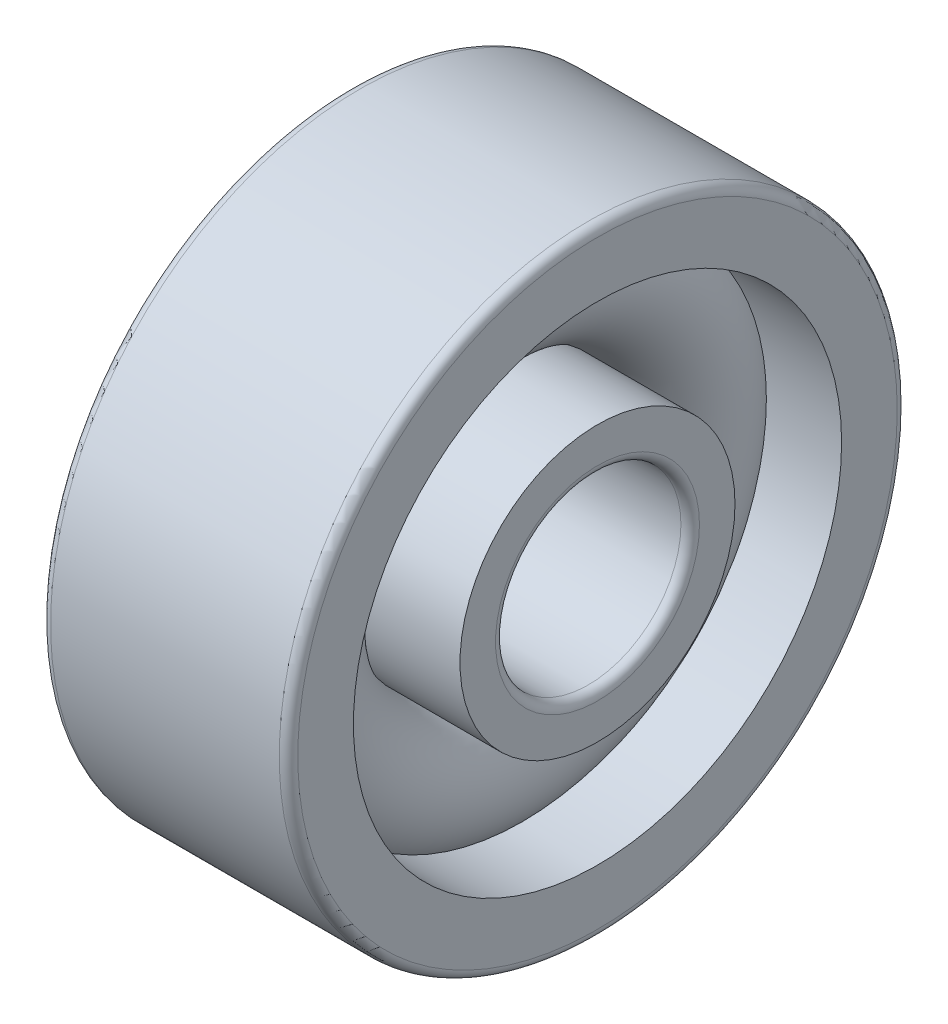
SolidWorks part; units mm, degrees
ref_plane "Plane1" through (0, 0, 0) normal (0, 0, 1) x (1, 0, 0)
ref_plane "Plane2" through (0, 0, 0) normal (0, 1, 0) x (1, 0, 0)
ref_plane "Plane3" through (0, 0, 0) normal (1, 0, 0) x (0, 0, -1)
other "Configuration Table"
sketch "Clipboard" plane through (0, 0, 0) normal (0, 0, 1) x (1, 0, 0)
  line L0 (-10, 0) -> (10, 0) construction
  line L1 (0, 0) -> (22.3471, -0.7804)
  line L2 (0, 0) -> (3.248, 0.1134)
  line L3 (0, 0) -> (22.3471, -0.7804)
  line L4 (0, 0) -> (-22.3573, -0.3902)
  dimension "BallCLRad" = 3.25
sketch "CagSpiSke" plane through (0, 0, 0) normal (0, 0, 1) x (1, 0, 0)
  line L0 (0.2625, 3.075) -> (0.2625, 3.425)
  line L1 (0.2625, 3.425) -> (-0.2625, 3.425)
  line L2 (-0.2625, 3.425) -> (-0.2625, 3.075)
  line L3 (-0.2625, 3.075) -> (0.2625, 3.075)
  line L4 (-20.6375, 0) -> (20.6375, 0) construction
  line L5 (0, 0) -> (0, 23.7692) construction
  dimension "OD" = 6.85
  dimension "ID" = 6.15
revolve "CageSpine" add sketch "CagSpiSke" angle 0.001 about L4
ref_axis "Axis1" through (-50, 0, 0) along (1, 0, 0)
sketch "CagBalSke" plane through (0, 0, 0) normal (0, 0, 1) x (1, 0, 0)
  line L0 (-1.155, 3.25) -> (1.155, 3.25)
  line L1 (-1.905, 3.25) -> (1.905, 3.25) construction
  line L2 (-10, 0) -> (10, 0) construction
  line L3 (0, 0) -> (0, 24) construction
  arc A0 (1.155, 3.25) -> (-1.155, 3.25) centre (0, 3.25) cw
  dimension "BallCLRad" = 3.25
revolve "CageBall" [suppressed] add sketch "CagBalSke" angle 360 about L1 reverse direction yes
pattern_circular "CageBalls" [suppressed] count 2 every 180 about axis through (-50, 0, 0) along (1, 0, 0)
sketch "CagTrmODSke" plane through (0, 0, 0) normal (0, 0, 1) x (1, 0, 0)
  line L0 (1.156, 3.425) -> (1.156, 4.406)
  line L1 (1.156, 4.406) -> (-1.156, 4.406)
  line L2 (-1.156, 4.406) -> (-1.156, 3.425)
  line L3 (-1.156, 3.425) -> (1.156, 3.425)
  line L4 (-20.6375, 0) -> (20.6375, 0) construction
  line L5 (0, 0) -> (0, 25) construction
  dimension "Width" = 2.312
  dimension "ID" = 6.85
  dimension "OD" = 8.812
revolve "CageTrimOD" [suppressed] cut sketch "CagTrmODSke" angle 360 about L4 reverse direction yes
sketch "CagTrmIDSke" plane through (0, 0, 0) normal (0, 0, 1) x (1, 0, 0)
  line L0 (1.156, 2.096) -> (1.156, 3.075)
  line L1 (1.156, 3.075) -> (-1.156, 3.075)
  line L2 (-1.156, 3.075) -> (-1.156, 2.096)
  line L3 (-1.156, 2.096) -> (1.156, 2.096)
  line L4 (-20.6375, 0) -> (20.6375, 0) construction
  line L5 (0, 0) -> (0, 25) construction
  dimension "Width" = 2.312
  dimension "ID" = 4.192
  dimension "OD" = 6.15
revolve "CageTrimID" [suppressed] cut sketch "CagTrmIDSke" angle 360 about L4 reverse direction yes
sketch "BalSimSke" plane through (0, 0, 0) normal (0, 0, 1) x (1, 0, 0)
  line L0 (-10, 0) -> (10, 0) construction
  line L1 (-10, 3.25) -> (10, 3.25) construction
  line L2 (0, 0) -> (0, 23) construction
  circle A0 centre (0, 3.25) radius 1.05
  dimension "BallCLRad" = 3.25
  dimension "Ball_diameter" = 2.1
revolve "BallsSimplified" add sketch "BalSimSke" angle 360 about L0
sketch "BalDetSke" plane through (0, 0, 0) normal (0, 0, 1) x (1, 0, 0)
  line L0 (-1.05, 3.25) -> (1.05, 3.25)
  line L1 (-1.905, 3.25) -> (1.905, 3.25) construction
  line L2 (0, 0) -> (0, 25) construction
  arc A0 (1.05, 3.25) -> (-1.05, 3.25) centre (0, 3.25) cw
  dimension "BallCLRad" = 3.25
  dimension "Ball_diameter" = 2.1
revolve "BallDetailed" [suppressed] add sketch "BalDetSke" angle 360 about L1 reverse direction yes
sketch "InnRacSke" plane through (0, 0, 0) normal (0, 0, 1) x (1, 0, 0)
  line L0 (-0.7487, 2.55) -> (-2, 2.55)
  line L1 (-2, 2.55) -> (-2, 1.65)
  line L2 (-1.85, 1.5) -> (1.85, 1.5)
  line L3 (2, 1.65) -> (2, 2.225)
  line L4 (0, 2.225) -> (2, 2.225)
  line L5 (-20.6375, 0) -> (20.6375, 0) construction
  line L6 (0, 0) -> (0, 30) construction
  arc A0 (-2, 1.65) -> (-1.85, 1.5) centre (-1.85, 1.65) ccw
  arc A1 (1.85, 1.5) -> (2, 1.65) centre (1.85, 1.65) ccw
  arc A2 (0, 2.225) -> (-0.7487, 2.55) centre (0, 3.25) cw
  dimension "BallCLRad" = 3.25
  dimension "Fillet_radius" = 0.15
  dimension "Ball_diameter" = 2.05
  dimension "ID" = 3
  dimension "OD" = 5.1
  dimension "Width" = 4
revolve "InnerRace" add sketch "InnRacSke" angle 360 about L5 reverse direction yes
sketch "OutRacSke" plane through (0, 0, 0) normal (0, 0, 1) x (1, 0, 0)
  line L0 (0, 4.275) -> (-2, 4.275)
  line L1 (-2, 4.275) -> (-2, 4.85)
  line L2 (-1.85, 5) -> (1.85, 5)
  line L3 (2, 4.85) -> (2, 3.95)
  line L4 (2, 3.95) -> (0.7487, 3.95)
  line L5 (-20.6375, 0) -> (20.6375, 0) construction
  line L6 (0, 0) -> (0, 30) construction
  arc A0 (-2, 4.85) -> (-1.85, 5) centre (-1.85, 4.85) cw
  arc A1 (1.85, 5) -> (2, 4.85) centre (1.85, 4.85) cw
  arc A2 (0.7487, 3.95) -> (0, 4.275) centre (0, 3.25) ccw
  dimension "BallCLRad" = 3.25
  dimension "Fillet_radius" = 0.15
  dimension "Ball_diameter" = 2.05
  dimension "Width" = 4
revolve "OuterRace" add sketch "OutRacSke" angle 360 about L5 reverse direction yes
pattern_circular "BallsDetailed" [suppressed] count 2 every 180 about axis through (-50, 0, 0) along (1, 0, 0)
equation "\"BallCLRad@Clipboard\" = ( \"OD@OutRacSke\" + \"ID@InnRacSke\" ) / 4"
equation "\"BallCLRad@BalSimSke\" = \"BallCLRad@Clipboard\""
equation "\"BallCLRad@BalDetSke\" = \"BallCLRad@Clipboard\""
equation "\"BallCLRad@InnRacSke\" = \"BallCLRad@Clipboard\""
equation "\"BallCLRad@OutRacSke\" = \"BallCLRad@Clipboard\""
equation "\"Ball_diameter@InnRacSke\" = \"Ball_diameter@BalDetSke\" - 0.05"
equation "\"Ball_diameter@OutRacSke\" = \"Ball_diameter@BalDetSke\" - 0.05"
equation "\"Ball_diameter@BalSimSke\" = \"Ball_diameter@BalDetSke\""
equation "\"Width@OutRacSke\" = \"Width@InnRacSke\""
equation "\"Fillet_radius@OutRacSke\" = \"Fillet_radius@InnRacSke\""
equation "\"Max_count@Clipboard\" = int( 3.14159265 / atn(( \"Ball_diameter@BalDetSke\" / 2) / sqr( \"BallCLRad@Clipboard\"  *  \"BallCLRad@Clipboard\" - ( \"Ball_diameter@BalDetSke\" / 2) *  ( \"Ball_diameter@BalDetSke\" / 2))))"
equation "\"Max_count@Clipboard\" = ((sgn( \"Max_count@Clipboard\" - \"Count@Clipboard\" )-1)*( \"Max_count@Clipboard\" - \"Count@Clipboard\" ))/-2+ \"Count@Clipboard\""
equation "\"Count@BallsDetailed\" = int( \"Show_count@Clipboard\" ) "
equation "\"Count@BallsDetailed\" = ((sgn( \"Count@BallsDetailed\" - \"Max_count@Clipboard\" )-1)*( \"Count@BallsDetailed\" - \"Max_count@Clipboard\" ))/-2+ \"Max_count@Clipboard\""
equation "\"Count@BallsDetailed\" = ((sgn( \"Count@BallsDetailed\" - \"Min_count@Clipboard\" )+1)*( \"Count@BallsDetailed\" - \"Min_count@Clipboard\"))/2 +\"Min_count@Clipboard\""
equation "\"Angle@BallsDetailed\" = 360.0 / \"Max_count@Clipboard\""
equation "\"BallCLRad@CagBalSke\" = \"BallCLRad@Clipboard\""
equation "\"Count@CageBalls\" = \"Count@BallsDetailed\""
equation "\"Angle@CageBalls\" = \"Angle@BallsDetailed\""
equation "\"Angle@CageSpine\" =  \"Angle@CageBalls\" * ( \"Count@CageBalls\" -1 + int( \"Count@CageBalls\" / \"Max_count@Clipboard\" ) )  + 0.001 -  int( \"Count@CageBalls\" / \"Max_count@Clipboard\" ) * 0.001"
equation "\"Angle@CageSpine\" =  \"Angle@CageSpine\" * int( \"Min_count@Clipboard\" / 2) + int(1 / \"Min_count@Clipboard\")  * 0.001"
equation "\"CageWallOD@CagBalSke\" =  \"Ball_diameter@BalDetSke\" * 1.1"
equation "\"Thickness@CagSpiSke\" =  \"Ball_diameter@BalDetSke\" * 0.25"
equation "\"OD@CagTrmODSke\" = \"BallCLRad@Clipboard\" * 2 + \"CageWallOD@CagBalSke\" + 0.002"
equation "\"ID@CagTrmODSke\" = \"BallCLRad@Clipboard\" * 2 + \"Ball_diameter@BalDetSke\" / 6"
equation "\"OD@CagTrmIDSke\" = \"BallCLRad@Clipboard\" * 2 - \"Ball_diameter@BalDetSke\" / 6"
equation "\"ID@CagTrmIDSke\" = \"BallCLRad@Clipboard\" * 2 - \"CageWallOD@CagBalSke\" + 0.002"
equation "\"OD@CagSpiSke\" = \"ID@CagTrmODSke\""
equation "\"ID@CagSpiSke\" = \"OD@CagTrmIDSke\""
equation "\"Width@CagTrmODSke\" = \"CageWallOD@CagBalSke\" + 0.002"
equation "\"Width@CagTrmIDSke\" = \"CageWallOD@CagBalSke\" + 0.002"
